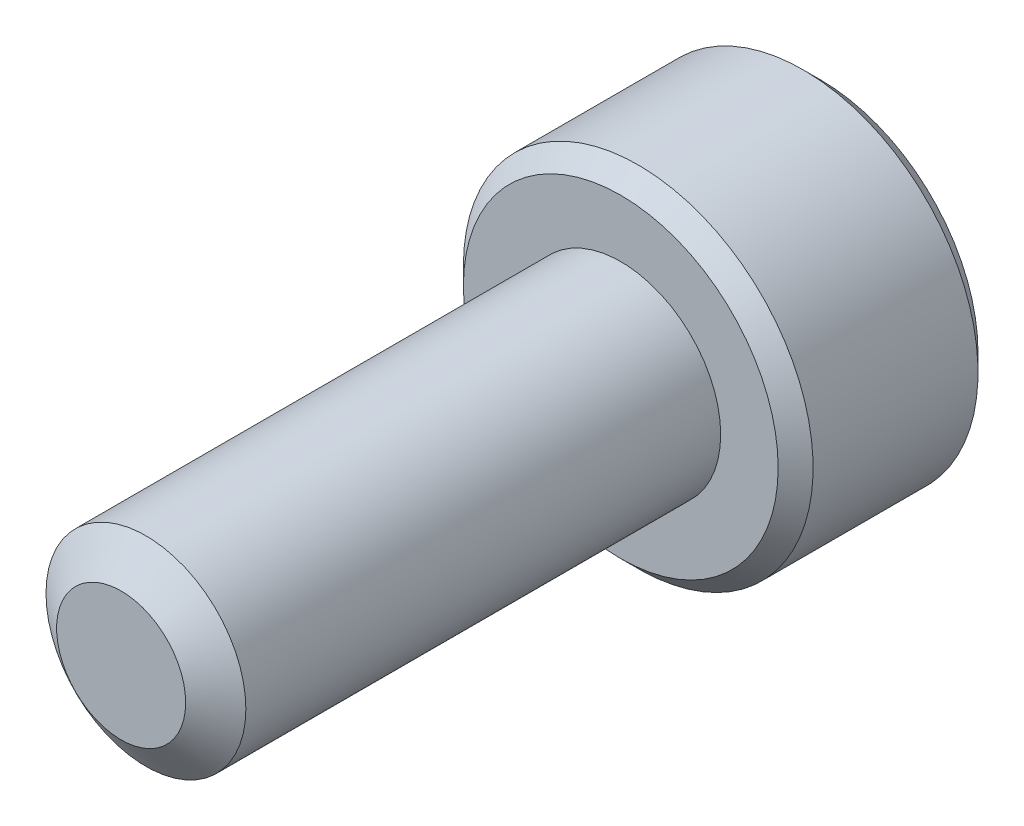
SolidWorks part; units mm, degrees
other "DetailItem1"
ref_plane "Front Plane" through (0, 0, 0) normal (0, 0, 1) x (1, 0, 0)
ref_plane "Top Plane" through (0, 0, 0) normal (0, 1, 0) x (1, 0, 0)
ref_plane "Right Plane" through (0, 0, 0) normal (1, 0, 0) x (0, 0, -1)
sketch "Sketch1" plane through (0, 0, 0) normal (0, 0, 1) x (1, 0, 0)
  circle A0 centre (0, 0) radius 2
  dimension "OD" = 4
extrude "Extrude1" add sketch "Sketch1" against normal blind 10
sketch "Sketch2" plane through (0, 0, 0) normal (0, 0, 1) x (1, 0, 0)
  circle A0 centre (0, 0) radius 2 construction
  circle A1 centre (0, 0) radius 2
curve "Helix/Spiral1" [suppressed] pitch 0.7 height 10.7 turns 15.2857 parameters "pitch"=0.7
sketch "Sketch3" plane through (0, 0, 0) normal (1, 0, 0) x (0, 0, -1)
  line L0 (-0.6125, 2) -> (-0.35, 1.5453)
  line L1 (-0.35, 1.5453) -> (-0.2625, 1.5453)
  line L2 (-0.2625, 1.5453) -> (0, 2)
  line L3 (-0.6125, 2) -> (0, 2)
  line L4 (-0.3062, 2) -> (-0.3062, 1.5453) construction
  line L5 (-0.4812, 1.7727) -> (-0.1312, 1.7727) construction
  line L6 (0, 2) -> (0, -2) construction
  dimension "D1" = 0.0875
  dimension "D2" = 0.35
  dimension "D3" = 60
sweep "Cut-Sweep1" [suppressed] cut profiles "Sketch3" path "Helix/Spiral1"
sketch "Sketch4" plane through (0, 0, 0) normal (1, 0, 0) x (0, 0, -1)
  line L0 (0.4962, 2) -> (0, 1.2913)
  line L1 (0, 1.2913) -> (0, 2)
  line L2 (0.4962, 2) -> (0, 2)
  line L3 (-0.6125, 2) -> (0, 2) construction
  line L4 (0, 0) -> (7.0209, 0) construction
  dimension "D1" = 55
  dimension "D2" = 0.254
revolve "Cut-Revolve1" cut sketch "Sketch4" angle 360 about L4
sketch "Sketch6" plane through (0, 0, -10) normal (0, 0, -1) x (-1, 0, 0)
  circle A0 centre (0, 0) radius 3.5
  dimension "head dia" = 7
extrude "Extrude2" add sketch "Sketch6" along normal blind 4
sketch "Sketch7" plane through (0, 0, -14) normal (0, 0, -1) x (-1, 0, 0)
  line L1 (0, 1.7321) -> (-1.5, 0.866)
  line L2 (-1.5, 0.866) -> (-1.5, -0.866)
  line L3 (-1.5, -0.866) -> (0, -1.7321)
  line L4 (0, -1.7321) -> (1.5, -0.866)
  line L5 (1.5, -0.866) -> (1.5, 0.866)
  line L6 (1.5, 0.866) -> (0, 1.7321)
  circle A0 centre (0, 0) radius 1.5 construction
  dimension "hex dia" = 3
extrude "Cut-Extrude1" cut sketch "Sketch7" against normal blind 2.25
sketch "Sketch8" plane through (0, 0, -14) normal (0, 0, -1) x (-1, 0, 0)
  circle A0 centre (0, 0) radius 1.7321
extrude "Cut-Extrude2" cut sketch "Sketch8" against normal through all draft 45
chamfer "Chamfer1" distance 0.35 angle 45 2 edges at (-3.5, 0, -14) (-3.5, 0, -10)
sketch "Sketch10" plane through (0, 0, -10) normal (0, 0, 1) x (1, 0, 0)
  circle A1 centre (0, 0) radius 2
  circle A2 centre (0, 0) radius 2
  dimension "D1" = 0
ref_plane "Plane1" through (0, 0, 0) normal (0, 0, 1) x (1, 0, 0)
extrude "partial thread" [suppressed] add sketch "Sketch10" along normal up to surface (10 mm away) separate body up to plane "Plane1"
chamfer "Chamfer2" [suppressed] distance 0.08 angle 45
combine bodies "Combine1" [suppressed] operation type add bodies to combine 107 108
sketch "Sketch9" plane through (0, 0, 0) normal (1, 0, 0) x (0, 0, -1)
  line L0 (0, 2) -> (0, -2) construction
  line L1 (1.75, 2) -> (1.75, -2) construction
  dimension "D1" = 1.75
equation "\"D3@Helix/Spiral1\" = \"screw length@Extrude1\"+\"pitch@Helix/Spiral1\""
equation "\"D1@Sketch3\" = \"pitch@Helix/Spiral1\"*.125"
equation "\"D2@Sketch3\" = \"pitch@Helix/Spiral1\"*.5"
equation "\"D1@Cut-Extrude1\" = \"hex dia@Sketch7\"*.75"
equation "\"D1@Chamfer1\" = \"head dia@Sketch6\"*.05"
equation "\"D1@Sketch9\" = \"pitch@Helix/Spiral1\"*2.5"
equation "\"D1@Chamfer2\"=\"OD@Sketch1\"*.02"
